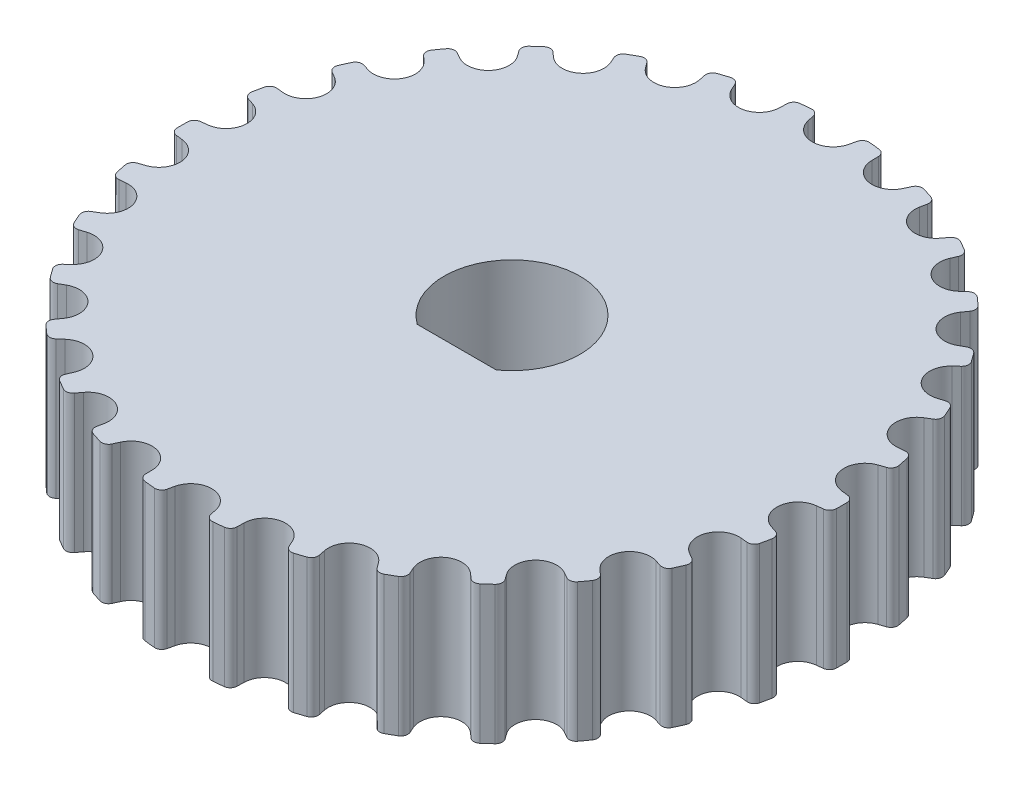
SolidWorks part; units mm, degrees
material "Acrylic (Medium-high impact)"
ref_plane "Front Plane" through (0, 0, 0) normal (0, 0, 1) x (1, 0, 0)
ref_plane "Top Plane" through (0, 0, 0) normal (0, 1, 0) x (1, 0, 0)
ref_plane "Right Plane" through (0, 0, 0) normal (1, 0, 0) x (0, 0, -1)
sketch "Sketch1" plane through (0, 0, 0) normal (0, 1, 0) x (1, 0, 0)
  circle A0 centre (0, 0) radius 14.3239
  dimension "D1" = 28.6479
extrude "Boss-Extrude1" add sketch "Sketch1" along normal blind 6
sketch "Sketch2" plane through (0, 6, 0) normal (0, 1, 0) x (1, 0, 0)
  line L0 (0, 0) -> (0, 14.3239) construction
  line L1 (-0.8883, 13.7564) -> (-0.95, 14.0339)
  line L2 (-2.9781, 14.0109) -> (-2.9781, 14.3239)
  line L3 (-2.9781, 14.3239) -> (2.9781, 14.3239)
  line L4 (0.8883, 13.7564) -> (0.95, 14.0339)
  line L5 (2.9781, 14.0109) -> (2.9781, 14.3239)
  circle A0 centre (0, 0) radius 14.3239 construction
  arc A1 (0.8883, 13.7564) -> (-0.8883, 13.7564) centre (0, 13.9539) cw
  arc A2 (-0.95, 14.0339) -> (-1.2694, 14.2676) centre (-1.2428, 13.9688) ccw
  arc A4 (0.95, 14.0339) -> (1.2694, 14.2676) centre (1.2428, 13.9688) cw
  arc A5 (-1.2694, 14.2676) -> (-2.9781, 14.0109) centre (0, 0) ccw
  arc A6 (1.2694, 14.2676) -> (2.9781, 14.0109) centre (0, 0) cw
  point P11 (0, 14.3239)
  point P19 (0, 13.0439)
  dimension "D3" = 0.3
  dimension "D5" = 0.91
  dimension "D2" = 0.95
  dimension "D4" = 1.28
  dimension "D6" = 12
extrude "Cut-Extrude1" cut sketch "Sketch2" against normal through all
pattern_circular "CirPattern1" count 30 over 360 about axis through (0, 6, 0) along (0, -1, 0) of "Cut-Extrude1"
sketch "Sketch3" plane through (0, 0, 0) normal (0, -1, 0) x (1, 0, 0)
  line L0 (1.7154, 2.4) -> (-1.7154, 2.4)
  arc A0 (-1.7154, 2.4) -> (1.7154, 2.4) centre (0, 0) ccw
  dimension "D1" = 5.9
  dimension "D2" = 2.4
extrude "Cut-Extrude2" cut sketch "Sketch3" against normal through all
sketch "Sketch5" plane through (0, 0, 0) normal (0, -1, 0) x (1, 0, 0)
  line L60 (6.3264, -12.2653) -> (6.4956, -12.4937)
  line L61 (7.5721, -11.8722) -> (7.4589, -11.6115)
  line L62 (8.7383, -10.682) -> (8.9513, -10.8702)
  line L63 (9.875, -10.0385) -> (9.7101, -9.807)
  line L64 (10.7682, -8.6318) -> (11.0157, -8.7716)
  line L65 (11.7463, -7.766) -> (11.5369, -7.5738)
  line L66 (12.3276, -6.2043) -> (12.5987, -6.2896)
  line L67 (13.1043, -5.1541) -> (12.8594, -5.0097)
  line L68 (13.3481, -3.5057) -> (13.6311, -3.5327)
  line L69 (13.8895, -2.3169) -> (13.62, -2.2266)
  line L70 (13.7853, -0.6538) -> (14.0677, -0.6215)
  line L71 (14.0677, 0.6215) -> (13.7853, 0.6538)
  line L72 (13.62, 2.2266) -> (13.8895, 2.3169)
  line L73 (13.6311, 3.5327) -> (13.3481, 3.5057)
  line L74 (12.8594, 5.0097) -> (13.1043, 5.1541)
  line L75 (12.5987, 6.2896) -> (12.3276, 6.2043)
  line L76 (11.5369, 7.5738) -> (11.7463, 7.766)
  line L77 (11.0157, 8.7716) -> (10.7682, 8.6318)
  line L78 (9.7101, 9.807) -> (9.875, 10.0385)
  line L79 (8.9513, 10.8702) -> (8.7383, 10.682)
  line L80 (7.4589, 11.6115) -> (7.5721, 11.8722)
  line L81 (6.4956, 12.4937) -> (6.3264, 12.2653)
  line L82 (4.8817, 12.9085) -> (4.9382, 13.1871)
  line L83 (3.7561, 13.5712) -> (3.638, 13.3126)
  line L84 (2.0912, 13.6414) -> (2.0886, 13.9257)
  line L85 (-0.8524, -14.0556) -> (-0.7907, -13.7781)
  line L86 (0.7907, -13.7781) -> (0.8524, -14.0556)
  line L87 (2.0886, -13.9257) -> (2.0912, -13.6414)
  line L88 (3.638, -13.3126) -> (3.7561, -13.5712)
  line L89 (4.9382, -13.1871) -> (4.8817, -12.9085)
  line L90 (6.3264, -12.2653) -> (6.4956, -12.4937)
  line L91 (7.5721, -11.8722) -> (7.4589, -11.6115)
  line L92 (8.7383, -10.682) -> (8.9513, -10.8702)
  line L93 (9.875, -10.0385) -> (9.7101, -9.807)
  line L94 (10.7682, -8.6318) -> (11.0157, -8.7716)
  line L95 (11.7463, -7.766) -> (11.5369, -7.5738)
  line L96 (12.3276, -6.2043) -> (12.5987, -6.2896)
  line L97 (13.1043, -5.1541) -> (12.8594, -5.0097)
  line L98 (13.3481, -3.5057) -> (13.6311, -3.5327)
  line L99 (13.8895, -2.3169) -> (13.62, -2.2266)
  line L100 (13.7853, -0.6538) -> (14.0677, -0.6215)
  line L101 (14.0677, 0.6215) -> (13.7853, 0.6538)
  line L102 (13.62, 2.2266) -> (13.8895, 2.3169)
  line L103 (13.6311, 3.5327) -> (13.3481, 3.5057)
  line L104 (12.8594, 5.0097) -> (13.1043, 5.1541)
  line L105 (12.5987, 6.2896) -> (12.3276, 6.2043)
  line L106 (11.5369, 7.5738) -> (11.7463, 7.766)
  line L107 (11.0157, 8.7716) -> (10.7682, 8.6318)
  line L108 (9.7101, 9.807) -> (9.875, 10.0385)
  line L109 (8.9513, 10.8702) -> (8.7383, 10.682)
  line L110 (7.4589, 11.6115) -> (7.5721, 11.8722)
  line L111 (6.4956, 12.4937) -> (6.3264, 12.2653)
  line L112 (4.8817, 12.9085) -> (4.9382, 13.1871)
  line L113 (3.7561, 13.5712) -> (3.638, 13.3126)
  line L114 (2.0912, 13.6414) -> (2.0886, 13.9257)
  line L115 (-0.8524, -14.0556) -> (-0.7907, -13.7781)
  line L116 (0.7907, -13.7781) -> (0.8524, -14.0556)
  line L117 (2.0886, -13.9257) -> (2.0912, -13.6414)
  line L118 (3.638, -13.3126) -> (3.7561, -13.5712)
  line L119 (4.9382, -13.1871) -> (4.8817, -12.9085)
  line L120 (0.8524, 14.0556) -> (0.7907, 13.7781)
  line L121 (0.8524, 14.0556) -> (0.7907, 13.7781)
  line L122 (-0.7907, 13.7781) -> (-0.8524, 14.0556)
  line L123 (-0.7907, 13.7781) -> (-0.8524, 14.0556)
  line L124 (-2.0886, 13.9257) -> (-2.0912, 13.6414)
  line L125 (-2.0886, 13.9257) -> (-2.0912, 13.6414)
  line L126 (-3.638, 13.3126) -> (-3.7561, 13.5712)
  line L127 (-3.638, 13.3126) -> (-3.7561, 13.5712)
  line L128 (-4.9382, 13.1871) -> (-4.8817, 12.9085)
  line L129 (-4.9382, 13.1871) -> (-4.8817, 12.9085)
  line L130 (-6.3264, 12.2653) -> (-6.4956, 12.4937)
  line L131 (-6.3264, 12.2653) -> (-6.4956, 12.4937)
  line L132 (-7.5721, 11.8722) -> (-7.4589, 11.6115)
  line L133 (-7.5721, 11.8722) -> (-7.4589, 11.6115)
  line L134 (-8.7383, 10.682) -> (-8.9513, 10.8702)
  line L135 (-8.7383, 10.682) -> (-8.9513, 10.8702)
  line L136 (-9.875, 10.0385) -> (-9.7101, 9.807)
  line L137 (-9.875, 10.0385) -> (-9.7101, 9.807)
  line L138 (-10.7682, 8.6318) -> (-11.0157, 8.7716)
  line L139 (-10.7682, 8.6318) -> (-11.0157, 8.7716)
  line L140 (-11.7463, 7.766) -> (-11.5369, 7.5738)
  line L141 (-11.7463, 7.766) -> (-11.5369, 7.5738)
  line L142 (-12.3276, 6.2043) -> (-12.5987, 6.2896)
  line L143 (-12.3276, 6.2043) -> (-12.5987, 6.2896)
  line L144 (-13.1043, 5.1541) -> (-12.8594, 5.0097)
  line L145 (-13.1043, 5.1541) -> (-12.8594, 5.0097)
  line L146 (-13.3481, 3.5057) -> (-13.6311, 3.5327)
  line L147 (-13.3481, 3.5057) -> (-13.6311, 3.5327)
  line L148 (-13.8895, 2.3169) -> (-13.62, 2.2266)
  line L149 (-13.8895, 2.3169) -> (-13.62, 2.2266)
  line L150 (-13.7853, 0.6538) -> (-14.0677, 0.6215)
  line L151 (-13.7853, 0.6538) -> (-14.0677, 0.6215)
  line L152 (-14.0677, -0.6215) -> (-13.7853, -0.6538)
  line L153 (-14.0677, -0.6215) -> (-13.7853, -0.6538)
  line L154 (-13.62, -2.2266) -> (-13.8895, -2.3169)
  line L155 (-13.62, -2.2266) -> (-13.8895, -2.3169)
  line L156 (-13.6311, -3.5327) -> (-13.3481, -3.5057)
  line L157 (-13.6311, -3.5327) -> (-13.3481, -3.5057)
  line L158 (-12.8594, -5.0097) -> (-13.1043, -5.1541)
  line L159 (-12.8594, -5.0097) -> (-13.1043, -5.1541)
  line L160 (-12.5987, -6.2896) -> (-12.3276, -6.2043)
  line L161 (-12.5987, -6.2896) -> (-12.3276, -6.2043)
  line L162 (-11.5369, -7.5738) -> (-11.7463, -7.766)
  line L163 (-11.5369, -7.5738) -> (-11.7463, -7.766)
  line L164 (-11.0157, -8.7716) -> (-10.7682, -8.6318)
  line L165 (-11.0157, -8.7716) -> (-10.7682, -8.6318)
  line L166 (-9.7101, -9.807) -> (-9.875, -10.0385)
  line L167 (-9.7101, -9.807) -> (-9.875, -10.0385)
  line L168 (-8.9513, -10.8702) -> (-8.7383, -10.682)
  line L169 (-8.9513, -10.8702) -> (-8.7383, -10.682)
  line L170 (-7.4589, -11.6115) -> (-7.5721, -11.8722)
  line L171 (-7.4589, -11.6115) -> (-7.5721, -11.8722)
  line L172 (-6.4956, -12.4937) -> (-6.3264, -12.2653)
  line L173 (-6.4956, -12.4937) -> (-6.3264, -12.2653)
  line L174 (-4.8817, -12.9085) -> (-4.9382, -13.1871)
  line L175 (-4.8817, -12.9085) -> (-4.9382, -13.1871)
  line L176 (-3.7561, -13.5712) -> (-3.638, -13.3126)
  line L177 (-3.7561, -13.5712) -> (-3.638, -13.3126)
  line L178 (-2.0912, -13.6414) -> (-2.0886, -13.9257)
  line L179 (-2.0912, -13.6414) -> (-2.0886, -13.9257)
  circle A60 centre (0, 0) radius 3.9038
  arc A120 (6.4956, -12.4937) -> (7.0114, -12.6052) centre (6.817, -12.2556) ccw
  arc A121 (7.0114, -12.6052) -> (7.4107, -12.3747) centre (0, 0) ccw
  arc A122 (7.4107, -12.3747) -> (7.5721, -11.8722) centre (7.2051, -12.0315) ccw
  arc A123 (8.7383, -10.682) -> (7.4589, -11.6115) centre (8.2019, -11.289) ccw
  arc A124 (8.9513, -10.8702) -> (9.479, -10.8719) centre (9.2161, -10.5704) ccw
  arc A125 (9.479, -10.8719) -> (9.8216, -10.5635) centre (0, 0) ccw
  arc A126 (9.8216, -10.5635) -> (9.875, -10.0385) centre (9.5492, -10.2705) ccw
  arc A127 (10.7682, -8.6318) -> (9.7101, -9.807) centre (10.3698, -9.337) ccw
  arc A128 (11.0157, -8.7716) -> (11.5323, -8.6636) centre (11.2124, -8.4233) ccw
  arc A129 (11.5323, -8.6636) -> (11.8032, -8.2906) centre (0, 0) ccw
  arc A130 (11.8032, -8.2906) -> (11.7463, -7.766) centre (11.4759, -8.0607) ccw
  arc A131 (12.3276, -6.2043) -> (11.5369, -7.5738) centre (12.0845, -6.977) ccw
  arc A132 (12.5987, -6.2896) -> (13.0815, -6.0766) centre (12.7187, -5.908) ccw
  arc A133 (13.0815, -6.0766) -> (13.269, -5.6554) centre (0, 0) ccw
  arc A134 (13.269, -5.6554) -> (13.1043, -5.1541) centre (12.901, -5.4986) ccw
  arc A135 (13.3481, -3.5057) -> (12.8594, -5.0097) centre (13.271, -4.312) ccw
  arc A136 (13.6311, -3.5327) -> (14.059, -3.224) centre (13.6691, -3.1346) ccw
  arc A137 (14.059, -3.224) -> (14.1549, -2.7731) centre (0, 0) ccw
  arc A138 (14.1549, -2.7731) -> (13.8895, -2.3169) centre (13.7623, -2.6962) ccw
  arc A139 (13.7853, -0.6538) -> (13.62, -2.2266) centre (13.8775, -1.4586) ccw
  arc A140 (14.0677, -0.6215) -> (14.4221, -0.2305) centre (14.0222, -0.2241) ccw
  arc A141 (14.4221, -0.2305) -> (14.4221, 0.2305) centre (0, 0) ccw
  arc A142 (14.4221, 0.2305) -> (14.0677, 0.6215) centre (14.0222, 0.2241) ccw
  arc A143 (13.62, 2.2266) -> (13.7853, 0.6538) centre (13.8775, 1.4586) ccw
  arc A144 (13.8895, 2.3169) -> (14.1549, 2.7731) centre (13.7623, 2.6962) ccw
  arc A145 (14.1549, 2.7731) -> (14.059, 3.224) centre (0, 0) ccw
  arc A146 (14.059, 3.224) -> (13.6311, 3.5327) centre (13.6691, 3.1346) ccw
  arc A147 (12.8594, 5.0097) -> (13.3481, 3.5057) centre (13.271, 4.312) ccw
  arc A148 (13.1043, 5.1541) -> (13.269, 5.6554) centre (12.901, 5.4986) ccw
  arc A149 (13.269, 5.6554) -> (13.0815, 6.0766) centre (0, 0) ccw
  arc A150 (13.0815, 6.0766) -> (12.5987, 6.2896) centre (12.7187, 5.908) ccw
  arc A151 (11.5369, 7.5738) -> (12.3276, 6.2043) centre (12.0845, 6.977) ccw
  arc A152 (11.7463, 7.766) -> (11.8032, 8.2906) centre (11.4759, 8.0607) ccw
  arc A153 (11.8032, 8.2906) -> (11.5323, 8.6636) centre (0, 0) ccw
  arc A154 (11.5323, 8.6636) -> (11.0157, 8.7716) centre (11.2124, 8.4233) ccw
  arc A155 (9.7101, 9.807) -> (10.7682, 8.6318) centre (10.3698, 9.337) ccw
  arc A156 (9.875, 10.0385) -> (9.8216, 10.5635) centre (9.5492, 10.2705) ccw
  arc A157 (9.8216, 10.5635) -> (9.479, 10.8719) centre (0, 0) ccw
  arc A158 (9.479, 10.8719) -> (8.9513, 10.8702) centre (9.2161, 10.5704) ccw
  arc A159 (7.4589, 11.6115) -> (8.7383, 10.682) centre (8.2019, 11.289) ccw
  arc A160 (7.5721, 11.8722) -> (7.4107, 12.3747) centre (7.2051, 12.0315) ccw
  arc A161 (7.4107, 12.3747) -> (7.0114, 12.6052) centre (0, 0) ccw
  arc A162 (7.0114, 12.6052) -> (6.4956, 12.4937) centre (6.817, 12.2556) ccw
  arc A163 (4.8817, 12.9085) -> (6.3264, 12.2653) centre (5.6756, 12.7476) ccw
  arc A164 (4.9382, 13.1871) -> (4.6759, 13.645) centre (4.5462, 13.2666) ccw
  arc A165 (4.6759, 13.645) -> (4.2375, 13.7875) centre (0, 0) ccw
  arc A166 (4.2375, 13.7875) -> (3.7561, 13.5712) centre (4.12, 13.4051) ccw
  arc A167 (2.0912, 13.6414) -> (3.638, 13.3126) centre (2.9012, 13.649) ccw
  arc A168 (2.0886, 13.9257) -> (1.7367, 14.319) centre (1.6886, 13.9219) ccw
  arc A169 (1.7367, 14.319) -> (1.2783, 14.3672) centre (0, 0) ccw
  arc A170 (-1.2783, -14.3672) -> (-0.8524, -14.0556) centre (-1.2428, -13.9688) ccw
  arc A171 (0.7907, -13.7781) -> (-0.7907, -13.7781) centre (0, -13.9539) ccw
  arc A172 (0.8524, -14.0556) -> (1.2783, -14.3672) centre (1.2428, -13.9688) ccw
  arc A173 (1.2783, -14.3672) -> (1.7367, -14.319) centre (0, 0) ccw
  arc A174 (1.7367, -14.319) -> (2.0886, -13.9257) centre (1.6886, -13.9219) ccw
  arc A175 (3.638, -13.3126) -> (2.0912, -13.6414) centre (2.9012, -13.649) ccw
  arc A176 (3.7561, -13.5712) -> (4.2375, -13.7875) centre (4.12, -13.4051) ccw
  arc A177 (4.2375, -13.7875) -> (4.6759, -13.645) centre (0, 0) ccw
  arc A178 (4.6759, -13.645) -> (4.9382, -13.1871) centre (4.5462, -13.2666) ccw
  arc A179 (6.3264, -12.2653) -> (4.8817, -12.9085) centre (5.6756, -12.7476) ccw
  arc A180 (6.4956, -12.4937) -> (7.0114, -12.6052) centre (6.817, -12.2556) ccw
  arc A181 (7.0114, -12.6052) -> (7.4107, -12.3747) centre (0, 0) ccw
  arc A182 (7.4107, -12.3747) -> (7.5721, -11.8722) centre (7.2051, -12.0315) ccw
  arc A183 (8.7383, -10.682) -> (7.4589, -11.6115) centre (8.2019, -11.289) ccw
  arc A184 (8.9513, -10.8702) -> (9.479, -10.8719) centre (9.2161, -10.5704) ccw
  arc A185 (9.479, -10.8719) -> (9.8216, -10.5635) centre (0, 0) ccw
  arc A186 (9.8216, -10.5635) -> (9.875, -10.0385) centre (9.5492, -10.2705) ccw
  arc A187 (10.7682, -8.6318) -> (9.7101, -9.807) centre (10.3698, -9.337) ccw
  arc A188 (11.0157, -8.7716) -> (11.5323, -8.6636) centre (11.2124, -8.4233) ccw
  arc A189 (11.5323, -8.6636) -> (11.8032, -8.2906) centre (0, 0) ccw
  arc A190 (11.8032, -8.2906) -> (11.7463, -7.766) centre (11.4759, -8.0607) ccw
  arc A191 (12.3276, -6.2043) -> (11.5369, -7.5738) centre (12.0845, -6.977) ccw
  arc A192 (12.5987, -6.2896) -> (13.0815, -6.0766) centre (12.7187, -5.908) ccw
  arc A193 (13.0815, -6.0766) -> (13.269, -5.6554) centre (0, 0) ccw
  arc A194 (13.269, -5.6554) -> (13.1043, -5.1541) centre (12.901, -5.4986) ccw
  arc A195 (13.3481, -3.5057) -> (12.8594, -5.0097) centre (13.271, -4.312) ccw
  arc A196 (13.6311, -3.5327) -> (14.059, -3.224) centre (13.6691, -3.1346) ccw
  arc A197 (14.059, -3.224) -> (14.1549, -2.7731) centre (0, 0) ccw
  arc A198 (14.1549, -2.7731) -> (13.8895, -2.3169) centre (13.7623, -2.6962) ccw
  arc A199 (13.7853, -0.6538) -> (13.62, -2.2266) centre (13.8775, -1.4586) ccw
  arc A200 (14.0677, -0.6215) -> (14.4221, -0.2305) centre (14.0222, -0.2241) ccw
  arc A201 (14.4221, -0.2305) -> (14.4221, 0.2305) centre (0, 0) ccw
  arc A202 (14.4221, 0.2305) -> (14.0677, 0.6215) centre (14.0222, 0.2241) ccw
  arc A203 (13.62, 2.2266) -> (13.7853, 0.6538) centre (13.8775, 1.4586) ccw
  arc A204 (13.8895, 2.3169) -> (14.1549, 2.7731) centre (13.7623, 2.6962) ccw
  arc A205 (14.1549, 2.7731) -> (14.059, 3.224) centre (0, 0) ccw
  arc A206 (14.059, 3.224) -> (13.6311, 3.5327) centre (13.6691, 3.1346) ccw
  arc A207 (12.8594, 5.0097) -> (13.3481, 3.5057) centre (13.271, 4.312) ccw
  arc A208 (13.1043, 5.1541) -> (13.269, 5.6554) centre (12.901, 5.4986) ccw
  arc A209 (13.269, 5.6554) -> (13.0815, 6.0766) centre (0, 0) ccw
  arc A210 (13.0815, 6.0766) -> (12.5987, 6.2896) centre (12.7187, 5.908) ccw
  arc A211 (11.5369, 7.5738) -> (12.3276, 6.2043) centre (12.0845, 6.977) ccw
  arc A212 (11.7463, 7.766) -> (11.8032, 8.2906) centre (11.4759, 8.0607) ccw
  arc A213 (11.8032, 8.2906) -> (11.5323, 8.6636) centre (0, 0) ccw
  arc A214 (11.5323, 8.6636) -> (11.0157, 8.7716) centre (11.2124, 8.4233) ccw
  arc A215 (9.7101, 9.807) -> (10.7682, 8.6318) centre (10.3698, 9.337) ccw
  arc A216 (9.875, 10.0385) -> (9.8216, 10.5635) centre (9.5492, 10.2705) ccw
  arc A217 (9.8216, 10.5635) -> (9.479, 10.8719) centre (0, 0) ccw
  arc A218 (9.479, 10.8719) -> (8.9513, 10.8702) centre (9.2161, 10.5704) ccw
  arc A219 (7.4589, 11.6115) -> (8.7383, 10.682) centre (8.2019, 11.289) ccw
  arc A220 (7.5721, 11.8722) -> (7.4107, 12.3747) centre (7.2051, 12.0315) ccw
  arc A221 (7.4107, 12.3747) -> (7.0114, 12.6052) centre (0, 0) ccw
  arc A222 (7.0114, 12.6052) -> (6.4956, 12.4937) centre (6.817, 12.2556) ccw
  arc A223 (4.8817, 12.9085) -> (6.3264, 12.2653) centre (5.6756, 12.7476) ccw
  arc A224 (4.9382, 13.1871) -> (4.6759, 13.645) centre (4.5462, 13.2666) ccw
  arc A225 (4.6759, 13.645) -> (4.2375, 13.7875) centre (0, 0) ccw
  arc A226 (4.2375, 13.7875) -> (3.7561, 13.5712) centre (4.12, 13.4051) ccw
  arc A227 (2.0912, 13.6414) -> (3.638, 13.3126) centre (2.9012, 13.649) ccw
  arc A228 (2.0886, 13.9257) -> (1.7367, 14.319) centre (1.6886, 13.9219) ccw
  arc A229 (1.7367, 14.319) -> (1.2783, 14.3672) centre (0, 0) ccw
  arc A230 (-1.2783, -14.3672) -> (-0.8524, -14.0556) centre (-1.2428, -13.9688) ccw
  arc A231 (0.7907, -13.7781) -> (-0.7907, -13.7781) centre (0, -13.9539) ccw
  arc A232 (0.8524, -14.0556) -> (1.2783, -14.3672) centre (1.2428, -13.9688) ccw
  arc A233 (1.2783, -14.3672) -> (1.7367, -14.319) centre (0, 0) ccw
  arc A234 (1.7367, -14.319) -> (2.0886, -13.9257) centre (1.6886, -13.9219) ccw
  arc A235 (3.638, -13.3126) -> (2.0912, -13.6414) centre (2.9012, -13.649) ccw
  arc A236 (3.7561, -13.5712) -> (4.2375, -13.7875) centre (4.12, -13.4051) ccw
  arc A237 (4.2375, -13.7875) -> (4.6759, -13.645) centre (0, 0) ccw
  arc A238 (4.6759, -13.645) -> (4.9382, -13.1871) centre (4.5462, -13.2666) ccw
  arc A239 (6.3264, -12.2653) -> (4.8817, -12.9085) centre (5.6756, -12.7476) ccw
  arc A241 (1.2783, 14.3672) -> (0.8524, 14.0556) centre (1.2428, 13.9688) ccw
  arc A242 (1.2783, 14.3672) -> (0.8524, 14.0556) centre (1.2428, 13.9688) ccw
  arc A243 (-0.7907, 13.7781) -> (0.7907, 13.7781) centre (0, 13.9539) ccw
  arc A244 (-0.7907, 13.7781) -> (0.7907, 13.7781) centre (0, 13.9539) ccw
  arc A245 (-0.8524, 14.0556) -> (-1.2783, 14.3672) centre (-1.2428, 13.9688) ccw
  arc A246 (-0.8524, 14.0556) -> (-1.2783, 14.3672) centre (-1.2428, 13.9688) ccw
  arc A247 (-1.2783, 14.3672) -> (-1.7367, 14.319) centre (0, 0) ccw
  arc A248 (-1.2783, 14.3672) -> (-1.7367, 14.319) centre (0, 0) ccw
  arc A249 (-1.7367, 14.319) -> (-2.0886, 13.9257) centre (-1.6886, 13.9219) ccw
  arc A250 (-1.7367, 14.319) -> (-2.0886, 13.9257) centre (-1.6886, 13.9219) ccw
  arc A251 (-3.638, 13.3126) -> (-2.0912, 13.6414) centre (-2.9012, 13.649) ccw
  arc A252 (-3.638, 13.3126) -> (-2.0912, 13.6414) centre (-2.9012, 13.649) ccw
  arc A253 (-3.7561, 13.5712) -> (-4.2375, 13.7875) centre (-4.12, 13.4051) ccw
  arc A254 (-3.7561, 13.5712) -> (-4.2375, 13.7875) centre (-4.12, 13.4051) ccw
  arc A255 (-4.2375, 13.7875) -> (-4.6759, 13.645) centre (0, 0) ccw
  arc A256 (-4.2375, 13.7875) -> (-4.6759, 13.645) centre (0, 0) ccw
  arc A257 (-4.6759, 13.645) -> (-4.9382, 13.1871) centre (-4.5462, 13.2666) ccw
  arc A258 (-4.6759, 13.645) -> (-4.9382, 13.1871) centre (-4.5462, 13.2666) ccw
  arc A259 (-6.3264, 12.2653) -> (-4.8817, 12.9085) centre (-5.6756, 12.7476) ccw
  arc A260 (-6.3264, 12.2653) -> (-4.8817, 12.9085) centre (-5.6756, 12.7476) ccw
  arc A261 (-6.4956, 12.4937) -> (-7.0114, 12.6052) centre (-6.817, 12.2556) ccw
  arc A262 (-6.4956, 12.4937) -> (-7.0114, 12.6052) centre (-6.817, 12.2556) ccw
  arc A263 (-7.0114, 12.6052) -> (-7.4107, 12.3747) centre (0, 0) ccw
  arc A264 (-7.0114, 12.6052) -> (-7.4107, 12.3747) centre (0, 0) ccw
  arc A265 (-7.4107, 12.3747) -> (-7.5721, 11.8722) centre (-7.2051, 12.0315) ccw
  arc A266 (-7.4107, 12.3747) -> (-7.5721, 11.8722) centre (-7.2051, 12.0315) ccw
  arc A267 (-8.7383, 10.682) -> (-7.4589, 11.6115) centre (-8.2019, 11.289) ccw
  arc A268 (-8.7383, 10.682) -> (-7.4589, 11.6115) centre (-8.2019, 11.289) ccw
  arc A269 (-8.9513, 10.8702) -> (-9.479, 10.8719) centre (-9.2161, 10.5704) ccw
  arc A270 (-8.9513, 10.8702) -> (-9.479, 10.8719) centre (-9.2161, 10.5704) ccw
  arc A271 (-9.479, 10.8719) -> (-9.8216, 10.5635) centre (0, 0) ccw
  arc A272 (-9.479, 10.8719) -> (-9.8216, 10.5635) centre (0, 0) ccw
  arc A273 (-9.8216, 10.5635) -> (-9.875, 10.0385) centre (-9.5492, 10.2705) ccw
  arc A274 (-9.8216, 10.5635) -> (-9.875, 10.0385) centre (-9.5492, 10.2705) ccw
  arc A275 (-10.7682, 8.6318) -> (-9.7101, 9.807) centre (-10.3698, 9.337) ccw
  arc A276 (-10.7682, 8.6318) -> (-9.7101, 9.807) centre (-10.3698, 9.337) ccw
  arc A277 (-11.0157, 8.7716) -> (-11.5323, 8.6636) centre (-11.2124, 8.4233) ccw
  arc A278 (-11.0157, 8.7716) -> (-11.5323, 8.6636) centre (-11.2124, 8.4233) ccw
  arc A279 (-11.5323, 8.6636) -> (-11.8032, 8.2906) centre (0, 0) ccw
  arc A280 (-11.5323, 8.6636) -> (-11.8032, 8.2906) centre (0, 0) ccw
  arc A281 (-11.8032, 8.2906) -> (-11.7463, 7.766) centre (-11.4759, 8.0607) ccw
  arc A282 (-11.8032, 8.2906) -> (-11.7463, 7.766) centre (-11.4759, 8.0607) ccw
  arc A283 (-12.3276, 6.2043) -> (-11.5369, 7.5738) centre (-12.0845, 6.977) ccw
  arc A284 (-12.3276, 6.2043) -> (-11.5369, 7.5738) centre (-12.0845, 6.977) ccw
  arc A285 (-12.5987, 6.2896) -> (-13.0815, 6.0766) centre (-12.7187, 5.908) ccw
  arc A286 (-12.5987, 6.2896) -> (-13.0815, 6.0766) centre (-12.7187, 5.908) ccw
  arc A287 (-13.0815, 6.0766) -> (-13.269, 5.6554) centre (0, 0) ccw
  arc A288 (-13.0815, 6.0766) -> (-13.269, 5.6554) centre (0, 0) ccw
  arc A289 (-13.269, 5.6554) -> (-13.1043, 5.1541) centre (-12.901, 5.4986) ccw
  arc A290 (-13.269, 5.6554) -> (-13.1043, 5.1541) centre (-12.901, 5.4986) ccw
  arc A291 (-13.3481, 3.5057) -> (-12.8594, 5.0097) centre (-13.271, 4.312) ccw
  arc A292 (-13.3481, 3.5057) -> (-12.8594, 5.0097) centre (-13.271, 4.312) ccw
  arc A293 (-13.6311, 3.5327) -> (-14.059, 3.224) centre (-13.6691, 3.1346) ccw
  arc A294 (-13.6311, 3.5327) -> (-14.059, 3.224) centre (-13.6691, 3.1346) ccw
  arc A295 (-14.059, 3.224) -> (-14.1549, 2.7731) centre (0, 0) ccw
  arc A296 (-14.059, 3.224) -> (-14.1549, 2.7731) centre (0, 0) ccw
  arc A297 (-14.1549, 2.7731) -> (-13.8895, 2.3169) centre (-13.7623, 2.6962) ccw
  arc A298 (-14.1549, 2.7731) -> (-13.8895, 2.3169) centre (-13.7623, 2.6962) ccw
  arc A299 (-13.7853, 0.6538) -> (-13.62, 2.2266) centre (-13.8775, 1.4586) ccw
  arc A300 (-13.7853, 0.6538) -> (-13.62, 2.2266) centre (-13.8775, 1.4586) ccw
  arc A301 (-14.0677, 0.6215) -> (-14.4221, 0.2305) centre (-14.0222, 0.2241) ccw
  arc A302 (-14.0677, 0.6215) -> (-14.4221, 0.2305) centre (-14.0222, 0.2241) ccw
  arc A303 (-14.4221, 0.2305) -> (-14.4221, -0.2305) centre (0, 0) ccw
  arc A304 (-14.4221, 0.2305) -> (-14.4221, -0.2305) centre (0, 0) ccw
  arc A305 (-14.4221, -0.2305) -> (-14.0677, -0.6215) centre (-14.0222, -0.2241) ccw
  arc A306 (-14.4221, -0.2305) -> (-14.0677, -0.6215) centre (-14.0222, -0.2241) ccw
  arc A307 (-13.62, -2.2266) -> (-13.7853, -0.6538) centre (-13.8775, -1.4586) ccw
  arc A308 (-13.62, -2.2266) -> (-13.7853, -0.6538) centre (-13.8775, -1.4586) ccw
  arc A309 (-13.8895, -2.3169) -> (-14.1549, -2.7731) centre (-13.7623, -2.6962) ccw
  arc A310 (-13.8895, -2.3169) -> (-14.1549, -2.7731) centre (-13.7623, -2.6962) ccw
  arc A311 (-14.1549, -2.7731) -> (-14.059, -3.224) centre (0, 0) ccw
  arc A312 (-14.1549, -2.7731) -> (-14.059, -3.224) centre (0, 0) ccw
  arc A313 (-14.059, -3.224) -> (-13.6311, -3.5327) centre (-13.6691, -3.1346) ccw
  arc A314 (-14.059, -3.224) -> (-13.6311, -3.5327) centre (-13.6691, -3.1346) ccw
  arc A315 (-12.8594, -5.0097) -> (-13.3481, -3.5057) centre (-13.271, -4.312) ccw
  arc A316 (-12.8594, -5.0097) -> (-13.3481, -3.5057) centre (-13.271, -4.312) ccw
  arc A317 (-13.1043, -5.1541) -> (-13.269, -5.6554) centre (-12.901, -5.4986) ccw
  arc A318 (-13.1043, -5.1541) -> (-13.269, -5.6554) centre (-12.901, -5.4986) ccw
  arc A319 (-13.269, -5.6554) -> (-13.0815, -6.0766) centre (0, 0) ccw
  arc A320 (-13.269, -5.6554) -> (-13.0815, -6.0766) centre (0, 0) ccw
  arc A321 (-13.0815, -6.0766) -> (-12.5987, -6.2896) centre (-12.7187, -5.908) ccw
  arc A322 (-13.0815, -6.0766) -> (-12.5987, -6.2896) centre (-12.7187, -5.908) ccw
  arc A323 (-11.5369, -7.5738) -> (-12.3276, -6.2043) centre (-12.0845, -6.977) ccw
  arc A324 (-11.5369, -7.5738) -> (-12.3276, -6.2043) centre (-12.0845, -6.977) ccw
  arc A325 (-11.7463, -7.766) -> (-11.8032, -8.2906) centre (-11.4759, -8.0607) ccw
  arc A326 (-11.7463, -7.766) -> (-11.8032, -8.2906) centre (-11.4759, -8.0607) ccw
  arc A327 (-11.8032, -8.2906) -> (-11.5323, -8.6636) centre (0, 0) ccw
  arc A328 (-11.8032, -8.2906) -> (-11.5323, -8.6636) centre (0, 0) ccw
  arc A329 (-11.5323, -8.6636) -> (-11.0157, -8.7716) centre (-11.2124, -8.4233) ccw
  arc A330 (-11.5323, -8.6636) -> (-11.0157, -8.7716) centre (-11.2124, -8.4233) ccw
  arc A331 (-9.7101, -9.807) -> (-10.7682, -8.6318) centre (-10.3698, -9.337) ccw
  arc A332 (-9.7101, -9.807) -> (-10.7682, -8.6318) centre (-10.3698, -9.337) ccw
  arc A333 (-9.875, -10.0385) -> (-9.8216, -10.5635) centre (-9.5492, -10.2705) ccw
  arc A334 (-9.875, -10.0385) -> (-9.8216, -10.5635) centre (-9.5492, -10.2705) ccw
  arc A335 (-9.8216, -10.5635) -> (-9.479, -10.8719) centre (0, 0) ccw
  arc A336 (-9.8216, -10.5635) -> (-9.479, -10.8719) centre (0, 0) ccw
  arc A337 (-9.479, -10.8719) -> (-8.9513, -10.8702) centre (-9.2161, -10.5704) ccw
  arc A338 (-9.479, -10.8719) -> (-8.9513, -10.8702) centre (-9.2161, -10.5704) ccw
  arc A339 (-7.4589, -11.6115) -> (-8.7383, -10.682) centre (-8.2019, -11.289) ccw
  arc A340 (-7.4589, -11.6115) -> (-8.7383, -10.682) centre (-8.2019, -11.289) ccw
  arc A341 (-7.5721, -11.8722) -> (-7.4107, -12.3747) centre (-7.2051, -12.0315) ccw
  arc A342 (-7.5721, -11.8722) -> (-7.4107, -12.3747) centre (-7.2051, -12.0315) ccw
  arc A343 (-7.4107, -12.3747) -> (-7.0114, -12.6052) centre (0, 0) ccw
  arc A344 (-7.4107, -12.3747) -> (-7.0114, -12.6052) centre (0, 0) ccw
  arc A345 (-7.0114, -12.6052) -> (-6.4956, -12.4937) centre (-6.817, -12.2556) ccw
  arc A346 (-7.0114, -12.6052) -> (-6.4956, -12.4937) centre (-6.817, -12.2556) ccw
  arc A347 (-4.8817, -12.9085) -> (-6.3264, -12.2653) centre (-5.6756, -12.7476) ccw
  arc A348 (-4.8817, -12.9085) -> (-6.3264, -12.2653) centre (-5.6756, -12.7476) ccw
  arc A349 (-4.9382, -13.1871) -> (-4.6759, -13.645) centre (-4.5462, -13.2666) ccw
  arc A350 (-4.9382, -13.1871) -> (-4.6759, -13.645) centre (-4.5462, -13.2666) ccw
  arc A351 (-4.6759, -13.645) -> (-4.2375, -13.7875) centre (0, 0) ccw
  arc A352 (-4.6759, -13.645) -> (-4.2375, -13.7875) centre (0, 0) ccw
  arc A353 (-4.2375, -13.7875) -> (-3.7561, -13.5712) centre (-4.12, -13.4051) ccw
  arc A354 (-4.2375, -13.7875) -> (-3.7561, -13.5712) centre (-4.12, -13.4051) ccw
  arc A355 (-2.0912, -13.6414) -> (-3.638, -13.3126) centre (-2.9012, -13.649) ccw
  arc A356 (-2.0912, -13.6414) -> (-3.638, -13.3126) centre (-2.9012, -13.649) ccw
  arc A357 (-2.0886, -13.9257) -> (-1.7367, -14.319) centre (-1.6886, -13.9219) ccw
  arc A358 (-2.0886, -13.9257) -> (-1.7367, -14.319) centre (-1.6886, -13.9219) ccw
  arc A359 (-1.7367, -14.319) -> (-1.2783, -14.3672) centre (0, 0) ccw
  arc A360 (-1.7367, -14.319) -> (-1.2783, -14.3672) centre (0, 0) ccw
  dimension "D1" = 0.1
extrude "Boss-Extrude2" [suppressed] add sketch "Sketch5" against normal up to surface (5.8 mm away) up to face at (0, 6, -0.275)
sketch "Sketch6" plane through (0, 6, 0) normal (0, 1, 0) x (1, 0, 0)
  circle A0 centre (0, -10) radius 2.5
  dimension "D1" = 5
  dimension "D2" = 10
extrude "Cut-Extrude3" [suppressed] cut sketch "Sketch6" against normal through all
equation "\"smallPulleyTeeth\"= 30"
equation "\"largePulleyTeeth\"= 30"
equation "\"eighthThick\"= 3.0mm"
equation "\"D1@Sketch1\"=3*\"smallPulleyTeeth\"/pi"
equation "\"D1@Boss-Extrude1\" = \"eighthThick\" * 2"
equation "\"D6@Sketch2\"=360/\"smallPulleyTeeth\""
equation "\"quarterThick\"=6.0mm"
equation "\"D1@CirPattern1\"=\"smallPulleyTeeth\""
equation "\"sixteenthThick\"= 1.7mm"
equation "\"OD\"= 145mm"
equation "\"puckAngle\"= 60.5deg"
equation "\"puckDiam\"= 76.5mm"
equation "\"axlePress\"= 5.9mm"
equation "\"press\"= 0.2mm"
equation "\"wheelClear\"= 0.3mm"
equation "\"10-32clear\"= 4.8mm"
equation "\"6-32clear\"= 3.3mm"
equation "\"8-32clear\"= 4.0mm"
equation "\"wheelHeight\"= 22mm"
equation "\"D1@Sketch3\"=\"axlePress\""
